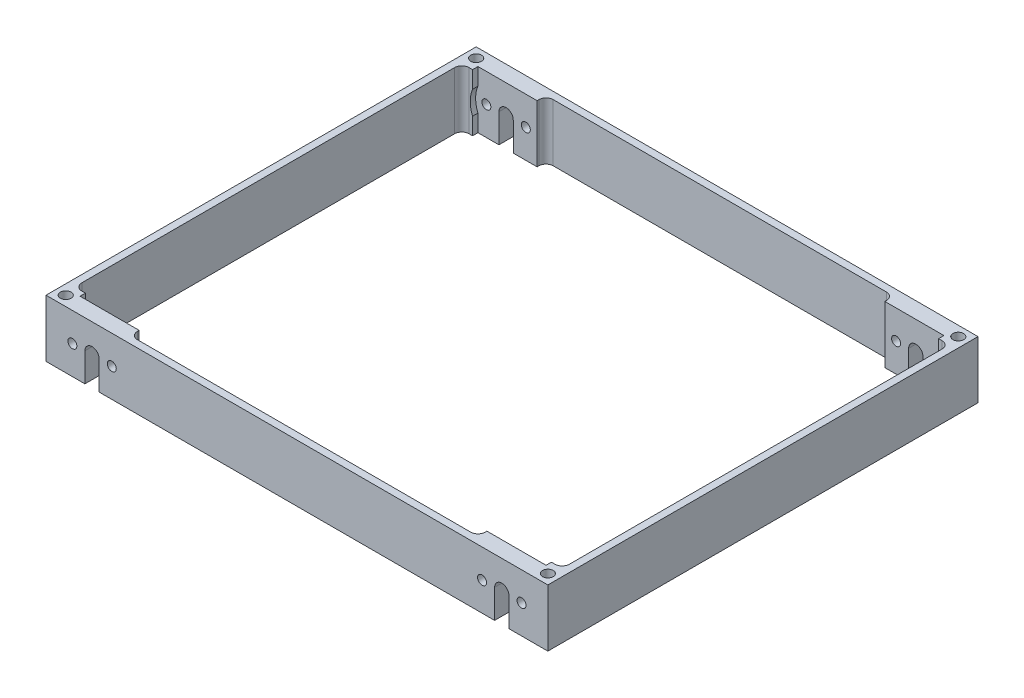
SolidWorks part; units mm, degrees
ref_plane "Front Plane" through (0, 0, 0) normal (0, 0, 1) x (1, 0, 0)
ref_plane "Top Plane" through (0, 0, 0) normal (0, 1, 0) x (1, 0, 0)
ref_plane "Right Plane" through (0, 0, 0) normal (1, 0, 0) x (0, 0, -1)
sketch "Sketch1" plane through (0, 0, 0) normal (0, 1, 0) x (1, 0, 0)
  line L0 (-135.5, 115.5) -> (-4.5, 115.5)
  line L1 (-140, 120) -> (0, 120)
  line L2 (-140, 120) -> (-140, 0)
  line L3 (-140, 0) -> (0, 0)
  line L4 (0, 120) -> (0, 0)
  line L5 (-4.5, 115.5) -> (-4.5, 4.5)
  line L6 (-135.5, 4.5) -> (-4.5, 4.5)
  line L7 (-135.5, 115.5) -> (-135.5, 4.5)
  dimension "D1" = 120
  dimension "D2" = 140
  dimension "D3" = 4.5
extrude "Boss-Extrude1" add sketch "Sketch1" along normal blind 16
sketch "Sketch3" plane through (0, 0, 0) normal (0, 0, 1) x (1, 0, 0)
  line L0 (-140, 8) -> (-129.15, 8) construction
  line L1 (-140, 16) -> (-140, 0) construction
  line L2 (0, 16) -> (0, 0) construction
  line L3 (-10.85, 8) -> (0, 8) construction
  line L4 (-127.15, 8) -> (-12.85, 8) construction
  line L5 (-129.15, 8) -> (-129.15, 0)
  line L6 (-140, 0) -> (0, 0) construction
  line L7 (-125.15, 8) -> (-125.15, 0)
  line L8 (-14.85, 8) -> (-14.85, 0)
  line L9 (-10.85, 8) -> (-10.85, 0)
  line L10 (-10.85, 0) -> (-14.85, 0)
  line L11 (-129.15, 0) -> (-125.15, 0)
  arc A0 (-125.15, 8) -> (-129.15, 8) centre (-127.15, 8) ccw
  arc A1 (-10.85, 8) -> (-14.85, 8) centre (-12.85, 8) ccw
  dimension "D1" = 4
  dimension "D2" = 114.3
extrude "Cut-Extrude1" cut sketch "Sketch3" against normal through all
sketch "Sketch5" plane through (0, 0, 0) normal (0, 0, 1) x (1, 0, 0)
  line L0 (-127.15, 8) -> (-132.65, 8) construction
  line L1 (-127.15, 8) -> (-121.65, 8) construction
  line L2 (-70, 16) -> (-70, 0) construction
  line L3 (-140, 16) -> (0, 16) construction
  line L4 (-125.15, 0) -> (-14.85, 0) construction
  circle A0 centre (-132.65, 8) radius 1.25
  circle A1 centre (-121.65, 8) radius 1.25
  circle A2 centre (-18.35, 8) radius 1.25
  circle A3 centre (-7.35, 8) radius 1.25
  dimension "D2" = 2.5
  dimension "D1" = 11
extrude "Cut-Extrude3" cut sketch "Sketch5" against normal through all
sketch "Sketch4" plane through (0, 16, 0) normal (0, 1, 0) x (1, 0, 0)
  line L1 (-138, 115.5) -> (-118.5, 115.5)
  line L2 (-138, 115.5) -> (-138, 4.5)
  line L3 (-138, 4.5) -> (-118.5, 4.5)
  line L4 (-2, 115.5) -> (-2, 4.5)
  line L5 (-135.5, 4.5) -> (-4.5, 4.5) construction
  line L6 (-4.5, 115.5) -> (-135.5, 115.5) construction
  line L7 (-140, 120) -> (-140, 0) construction
  line L8 (0, 0) -> (0, 120) construction
  line L9 (-118.5, 4.5) -> (-118.5, 2)
  line L10 (-118.5, 118) -> (-21.5, 118)
  line L11 (-118.5, 118) -> (-118.5, 115.5)
  line L12 (-118.5, 2) -> (-21.5, 2)
  line L13 (-21.5, 118) -> (-21.5, 115.5)
  line L14 (-21.5, 115.5) -> (-2, 115.5)
  line L15 (-21.5, 4.5) -> (-2, 4.5)
  line L16 (-21.5, 4.5) -> (-21.5, 2)
  line L19 (-70, 118) -> (-70, 2) construction
  dimension "D1" = 2
  dimension "D2" = 2
  dimension "D3" = 2.5
  dimension "D4" = 19.5
extrude "Cut-Extrude2" cut sketch "Sketch4" against normal through all
sketch "Sketch6" plane through (0, 0, 0) normal (0, 0, 1) x (1, 0, 0)
  line L0 (-138, 16) -> (-138, 0) construction
  line L1 (-140, 16) -> (0, 16) construction
  line L2 (-140, 0) -> (-129.15, 0) construction
  line L3 (-140, 16) -> (-140, 0) construction
  line L7 (-140, 16) -> (-135, 16)
  line L8 (-140, 8) -> (0, 8) construction
  line L9 (0, 16) -> (0, 0) construction
  line L10 (-70, 16) -> (-70, 0) construction
  line L11 (-125.15, 0) -> (-14.85, 0) construction
  line L24 (-140, 16) -> (-140, 0)
  line L25 (-135, 16) -> (-135, 11.26)
  line L26 (-135, 0) -> (-140, 0)
  line L27 (-5, 16) -> (-5, 11.26)
  line L28 (0, 16) -> (-5, 16)
  line L29 (0, 16) -> (0, 0)
  line L30 (-5, 0) -> (0, 0)
  line L31 (-135, 4.74) -> (-135, 0)
  line L32 (-5, 4.74) -> (-5, 0)
  arc A1 (-135, 11.26) -> (-135, 4.74) centre (-127.15, 8) ccw
  arc A2 (-5, 11.26) -> (-5, 4.74) centre (-12.85, 8) cw
  dimension "D1" = 2
  dimension "D2" = 5
extrude "Boss-Extrude2" add sketch "Sketch6" against normal up to surface (115.5 mm away) up to face at (-12.3, 6.25, -115.5)
sketch "Sketch7" plane through (0, 16, 0) normal (0, 1, 0) x (1, 0, 0)
  line L0 (-140, 120) -> (-140, 0) construction
  line L1 (-138, 114) -> (-2, 114)
  line L2 (-138, 114) -> (-138, 6)
  line L3 (-138, 6) -> (-2, 6)
  line L4 (-2, 114) -> (-2, 6)
  line L5 (0, 0) -> (0, 120) construction
  line L6 (0, 120) -> (-140, 120) construction
  line L7 (-140, 0) -> (0, 0) construction
  dimension "D1" = 2
  dimension "D2" = 2
  dimension "D3" = 6
  dimension "D4" = 6
extrude "Cut-Extrude4" cut sketch "Sketch7" against normal through all contours L2 L1 L4 L3
fillet "Fillet1" radius 2 8 edges at (-21.5, 8, -2) (-118.5, 8, -2) (-21.5, 8, -118) (-118.5, 8, -118) (-2, 8, -6) (-138, 8, -6) (-2, 8, -114) (-138, 8, -114)
ref_plane "Plane1" through (-118.5, 16, -4.5) normal (1, 0, 0) x (0, 0, -1)
sketch "Sketch9" plane through (0, 0, 0) normal (0, 1, 0) x (1, 0, 0)
  line L0 (-70, 120) -> (-70, 0) construction
  line L1 (0, 120) -> (-140, 120) construction
  line L2 (-140, 0) -> (0, 0) construction
  line L4 (-140, 120) -> (-140, 0) construction
  line L5 (-140, 60) -> (0, 60) construction
  line L6 (0, 0) -> (0, 120) construction
  circle A0 centre (-137.25, 2.75) radius 1.3
  circle A1 centre (-2.75, 2.75) radius 1.3
  circle A2 centre (-2.75, 117.25) radius 1.3
  circle A3 centre (-137.25, 117.25) radius 1.3
  dimension "D1" = 2.75
  dimension "D2" = 2.6
  dimension "D3" = 2.75
extrude "Cut-Extrude5" cut sketch "Sketch9" along normal blind 4
sketch "Sketch10" plane through (0, 16, 0) normal (0, 1, 0) x (1, 0, 0)
  line L0 (-70, 120) -> (-70, 0) construction
  line L1 (0, 120) -> (-140, 120) construction
  line L2 (-140, 0) -> (0, 0) construction
  line L3 (-137.25, 117.25) -> (-137.25, 120) construction
  line L4 (-140, 120) -> (-140, 0) construction
  line L5 (-140, 60) -> (0, 60) construction
  line L6 (0, 0) -> (0, 120) construction
  line L7 (-137.25, 117.25) -> (-140, 117.25) construction
  circle A0 centre (-137.25, 117.25) radius 1.5
  circle A1 centre (-2.75, 117.25) radius 1.5
  circle A2 centre (-2.75, 2.75) radius 1.5
  circle A3 centre (-137.25, 2.75) radius 1.5
  dimension "D1" = 3
  dimension "D2" = 2.75
extrude "Cut-Extrude6" cut sketch "Sketch10" against normal through all
